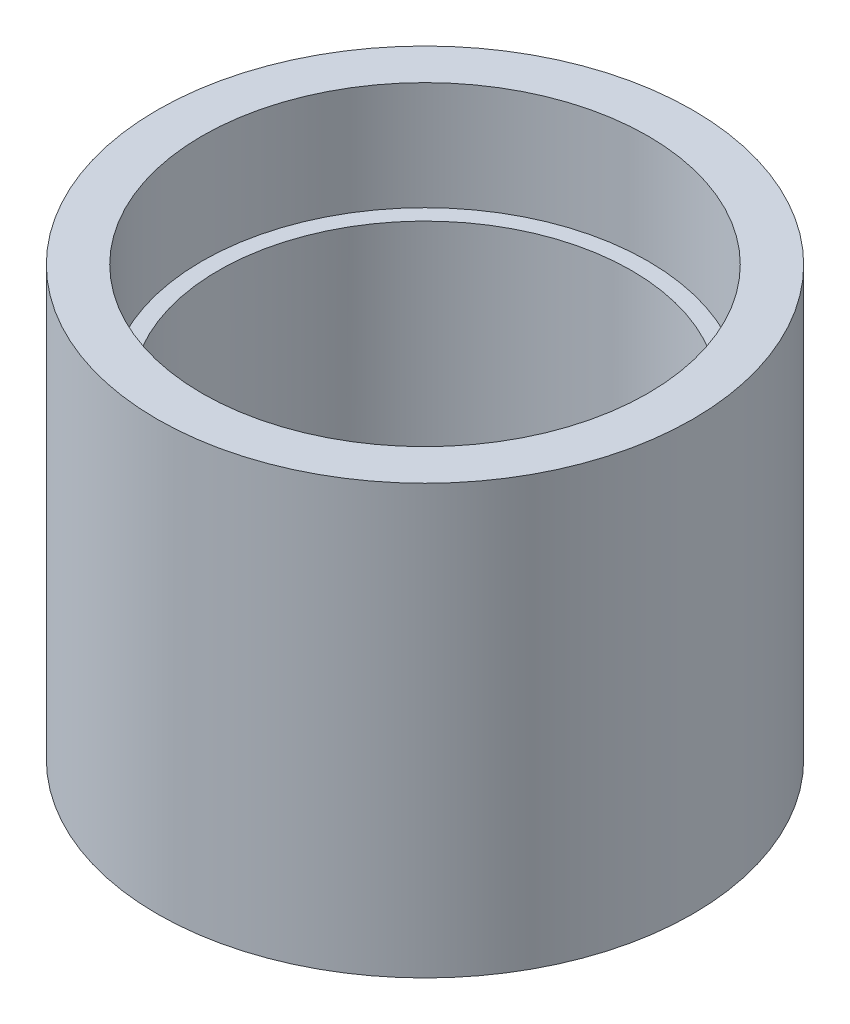
SolidWorks part; units mm, degrees
ref_plane "Front Plane" through (0, 0, 0) normal (0, 0, 1) x (1, 0, 0)
ref_plane "Top Plane" through (0, 0, 0) normal (0, 1, 0) x (1, 0, 0)
ref_plane "Right Plane" through (0, 0, 0) normal (1, 0, 0) x (0, 0, -1)
sketch "Sketch1" plane through (0, 0, 0) normal (0, 1, 0) x (1, 0, 0)
  circle A0 centre (0, 0) radius 22.225
  dimension "D1" = 44.45
extrude "Boss-Extrude1" add sketch "Sketch1" along normal blind 35.56
sketch "Sketch2" plane through (0, 35.56, 0) normal (0, 1, 0) x (1, 0, 0)
  circle A0 centre (0, 0) radius 18.5039
  dimension "D1" = 37.0078
extrude "Cut-Extrude1" cut sketch "Sketch2" against normal blind 8.9916
sketch "Sketch4" plane through (0, 0, 0) normal (0, -1, 0) x (1, 0, 0)
  circle A0 centre (0, 0) radius 18.5039
  dimension "D1" = 37.0078
extrude "Cut-Extrude2" cut sketch "Sketch4" against normal blind 8.9916
sketch "Sketch5" plane through (0, 8.9916, 0) normal (0, -1, 0) x (1, 0, 0)
  circle A0 centre (0, 0) radius 17.145
  dimension "D1" = 34.29
extrude "Cut-Extrude3" cut sketch "Sketch5" against normal through all
